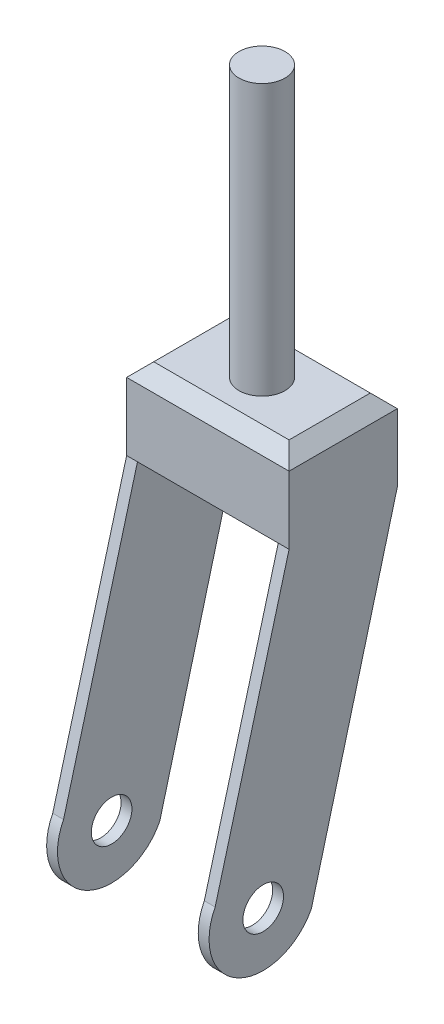
SolidWorks part; units mm, degrees
ref_plane "Plano frontal" through (0, 0, 0) normal (0, 0, 1) x (1, 0, 0)
ref_plane "Plano superior" through (0, 0, 0) normal (0, 1, 0) x (1, 0, 0)
ref_plane "Plano direito" through (0, 0, 0) normal (1, 0, 0) x (0, 0, -1)
sketch "Esboço1" plane through (0, 0, 0) normal (1, 0, 0) x (0, 0, -1)
  line L0 (-9.6437, -34.5481) -> (25.8624, -52.9685) construction
  line L1 (-1.1008, -61.5114) -> (8.1093, -43.7583) construction
  line L2 (17.6624, 66.2417) -> (17.6624, 96.2417)
  line L3 (17.6624, 96.2417) -> (57.6624, 96.2417)
  line L4 (57.6624, 96.2417) -> (57.6624, 66.2417)
  line L5 (37.6624, 96.2417) -> (37.6624, 66.2417) construction
  line L6 (25.8624, -52.9685) -> (57.6624, 66.2417)
  line L7 (-9.6437, -34.5481) -> (17.6624, 66.2417)
  line L8 (8.1093, -43.7583) -> (37.6624, 66.2417) construction
  circle A0 centre (8.1093, -43.7583) radius 7.5
  arc A1 (-9.6437, -34.5481) -> (25.8624, -52.9685) centre (8.1093, -43.7583) ccw
  dimension "D1" = 15
  dimension "D2" = 20
  dimension "D3" = 30
  dimension "D4" = 110
  dimension "D5" = 40
extrude "Ressalto-extrusão1" add sketch "Esboço1" along normal blind 30 and the other way blind 30
sketch "Esboço2" plane through (0, 0, -57.6624) normal (0, 0, -1) x (-1, 0, 0)
  line L0 (30, 66.2417) -> (-30, 66.2417) construction
  line L1 (-26, 66.2417) -> (26, 66.2417)
  line L2 (-26, 66.2417) -> (-26, -77.0434)
  line L3 (-26, -77.0434) -> (26, -77.0434)
  line L4 (26, 66.2417) -> (26, -77.0434)
  line L5 (-30, 66.2417) -> (-30, 96.2417) construction
  dimension "D1" = 4
  dimension "D2" = 4
extrude "Corte-extrusão1" cut sketch "Esboço2" against normal through all
sketch "Esboço3" plane through (0, 96.2417, 0) normal (0, 1, 0) x (1, 0, 0)
  line L0 (0, 57.6624) -> (0, 17.6624) construction
  line L1 (-30, 57.6624) -> (30, 57.6624) construction
  line L2 (-30, 17.6624) -> (30, 17.6624) construction
  circle A0 centre (0, 37.6624) radius 8.5
chamfer "Chanfro1" distance 5 angle 45 4 edges at (0, 96.2417, -17.6624) (-30, 96.2417, -37.6624) (30, 96.2417, -37.6624) (0, 96.2417, -57.6624)
extrude "Ressalto-extrusão2" add sketch "Esboço3" along normal blind 100 contours A0
